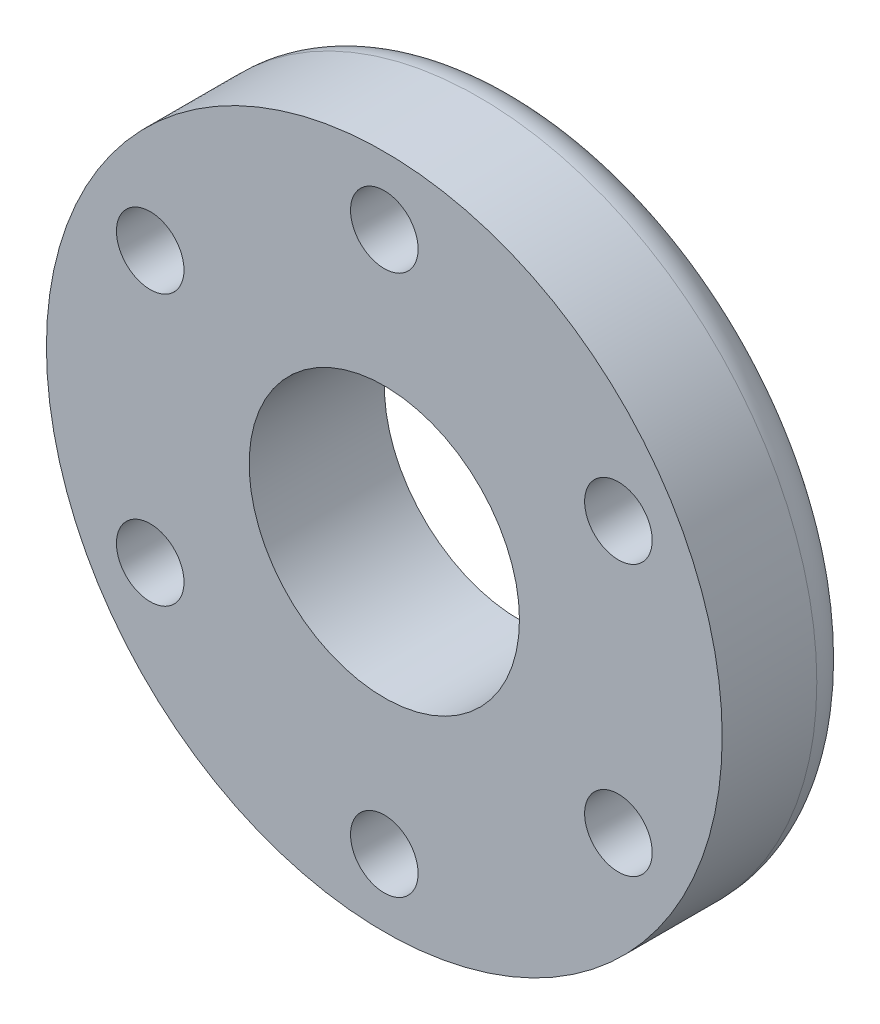
SolidWorks part; units mm, degrees
ref_plane "Front Plane" through (0, 0, 0) normal (0, 0, 1) x (1, 0, 0)
ref_plane "Top Plane" through (0, 0, 0) normal (0, 1, 0) x (1, 0, 0)
ref_plane "Right Plane" through (0, 0, 0) normal (1, 0, 0) x (0, 0, -1)
sketch "Sketch1" plane through (0, 0, 0) normal (0, 0, 1) x (1, 0, 0)
  circle A0 centre (0, 0) radius 25
  circle A1 centre (0, 0) radius 10
  dimension "D1" = 20
  dimension "D2" = 50
extrude "Boss-Extrude1" add sketch "Sketch1" along normal blind 10
sketch "Sketch2" plane through (0, 0, 10) normal (0, 0, 1) x (1, 0, 0)
  line L0 (0, 0) -> (0, 25.8649) construction
  circle A0 centre (0, 20) radius 2.5
  circle A1 centre (0, 0) radius 10 construction
  circle A5 centre (17.3205, 10) radius 2.5
  circle A6 centre (17.3205, -10) radius 2.5
  circle A7 centre (0, -20) radius 2.5
  circle A8 centre (-17.3205, -10) radius 2.5
  circle A9 centre (-17.3205, 10) radius 2.5
  point P16 (0, 0)
  point P20 (0, 0)
  dimension "D1" = 5
  dimension "D2" = 20
  dimension "D3" = 6
extrude "Cut-Extrude1" cut sketch "Sketch2" against normal blind 10
fillet "Fillet1" radius 3 1 edges at (25, 0, 0)
